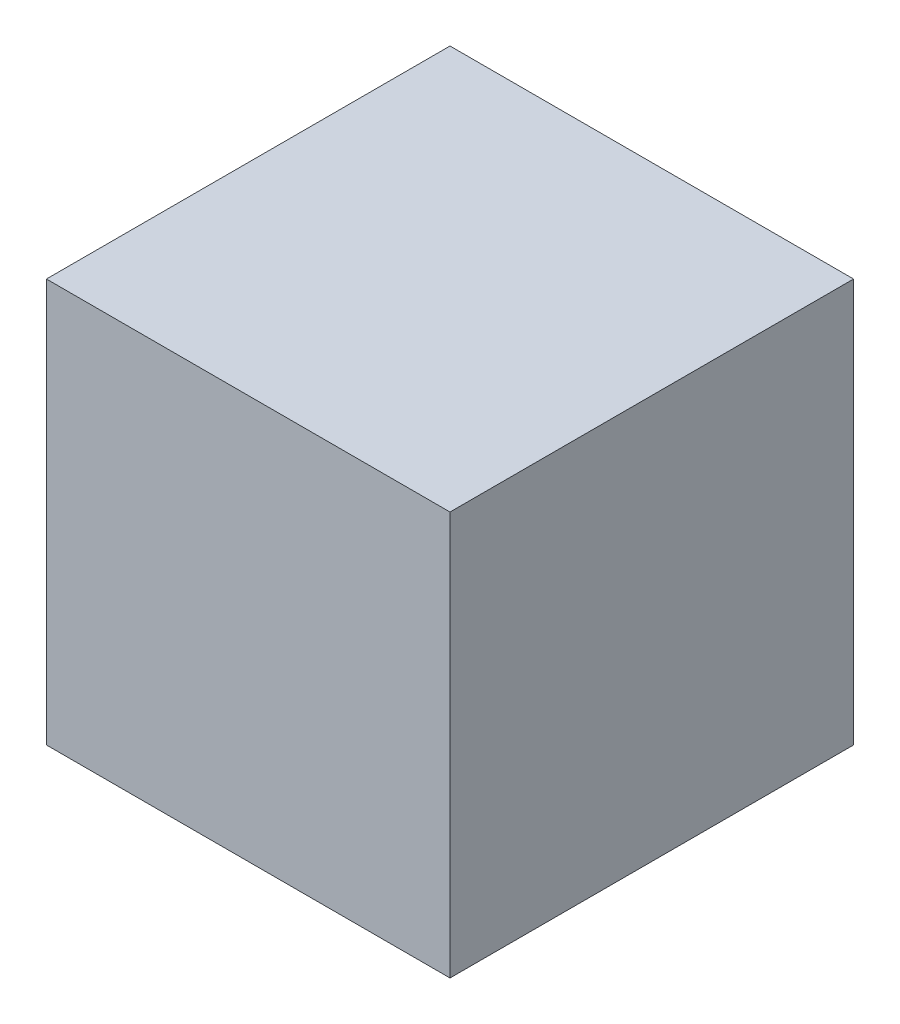
SolidWorks part; units mm, degrees
ref_plane "Front Plane" through (0, 0, 0) normal (0, 0, 1) x (1, 0, 0)
ref_plane "Top Plane" through (0, 0, 0) normal (0, 1, 0) x (1, 0, 0)
ref_plane "Right Plane" through (0, 0, 0) normal (1, 0, 0) x (0, 0, -1)
sketch "Sketch10" plane through (0, 0, 0) normal (0, 1, 0) x (1, 0, 0)
  line L0 (0, -51) -> (0, 51) construction
  line L1 (-51, 51) -> (51, 51)
  line L2 (-51, 51) -> (-51, -51)
  line L3 (-51, -51) -> (51, -51)
  line L4 (51, 51) -> (51, -51)
  line L5 (-51, 51) -> (51, -51) construction
  line L6 (-51, -51) -> (51, 51) construction
  line L7 (-51, 0) -> (51, 0) construction
  arc A0 (51, 0) -> (-51, 0) centre (0, 0) cw
  point P0 (0, 0)
  dimension "D1" = 102
  dimension "D2" = 102
extrude "Boss-Extrude6" add sketch "Sketch10" along normal blind 51 and the other way blind 51 contours L2 L3 L4 L1
